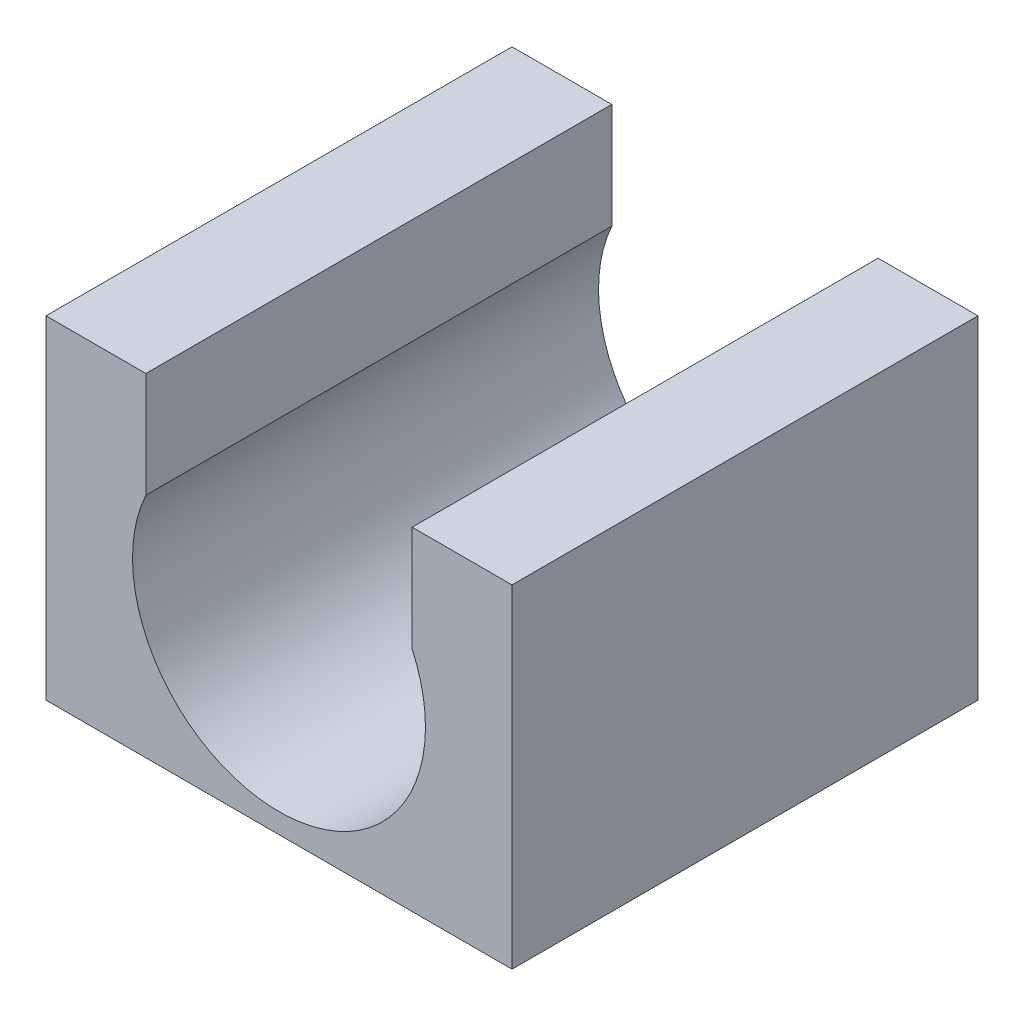
SolidWorks part; units mm, degrees
material "1060-H18"
ref_plane "前视基准面" through (0, 0, 0) normal (0, 0, 1) x (1, 0, 0)
ref_plane "上视基准面" through (0, 0, 0) normal (0, 1, 0) x (1, 0, 0)
ref_plane "右视基准面" through (0, 0, 0) normal (1, 0, 0) x (0, 0, -1)
sketch "草图1" plane through (0, 0, 0) normal (0, 0, 1) x (1, 0, 0)
  line L1 (-35, -25) -> (35, -25)
  line L2 (-35, -25) -> (-35, 25)
  line L3 (-35, 25) -> (35, 25)
  line L4 (35, -25) -> (35, 25)
  line L5 (-35, -25) -> (35, 25) construction
  line L6 (-35, 25) -> (35, -25) construction
  point P0 (0, 0)
  dimension "D1" = 70
  dimension "D2" = 50
extrude "凸台-拉伸1" add sketch "草图1" along normal mid plane 70
sketch "草图2" plane through (0, 0, 35) normal (0, 0, 1) x (1, 0, 0)
  circle A0 centre (0, 0) radius 22
  dimension "D1" = 44
extrude "切除-拉伸1" cut sketch "草图2" against normal through all
sketch "草图3" plane through (0, 25, 0) normal (0, 1, 0) x (1, 0, 0)
  line L0 (35, 35) -> (-35, 35) construction
  line L1 (-20, -35) -> (20, -35)
  line L2 (-20, -35) -> (-20, 35)
  line L3 (-20, 35) -> (20, 35)
  line L4 (20, -35) -> (20, 35)
  line L5 (-20, -35) -> (20, 35) construction
  line L6 (-20, 35) -> (20, -35) construction
  point P0 (0, 0)
  dimension "D1" = 40
extrude "切除-拉伸2" cut sketch "草图3" against normal blind 20
